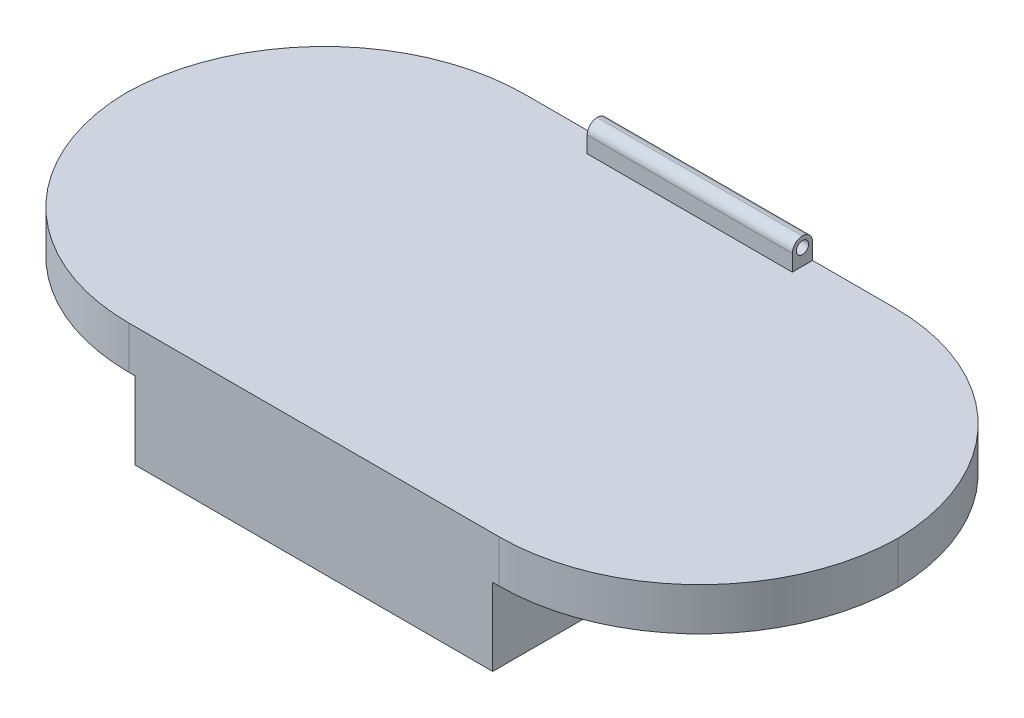
SolidWorks part; units mm, degrees
ref_plane "Front Plane" through (0, 0, 0) normal (0, 0, 1) x (1, 0, 0)
ref_plane "Top Plane" through (0, 0, 0) normal (0, 1, 0) x (1, 0, 0)
ref_plane "Right Plane" through (0, 0, 0) normal (1, 0, 0) x (0, 0, -1)
sketch "Sketch1" plane through (0, 0, 0) normal (0, 1, 0) x (1, 0, 0)
  line L1 (190, 97.5) -> (-190, 97.5)
  line L2 (190, 97.5) -> (190, -97.5)
  line L3 (190, -97.5) -> (-190, -97.5)
  line L4 (-190, 97.5) -> (-190, -97.5)
  line L5 (190, 97.5) -> (-190, -97.5) construction
  line L6 (190, -97.5) -> (-190, 97.5) construction
  point P0 (0, 0)
  dimension "D1" = 380
  dimension "D2" = 195
extrude "Boss-Extrude1" add sketch "Sketch1" along normal blind 59
sketch "Sketch2" plane through (190, 0, 0) normal (1, 0, 0) x (0, 0, -1)
  line L0 (-97.5, 59) -> (-97.5, 0) construction
  line L1 (97.5, 38) -> (-97.5, 38)
  line L2 (97.5, 38) -> (97.5, 0)
  line L3 (97.5, 0) -> (-97.5, 0)
  line L4 (-97.5, 38) -> (-97.5, 0)
  line L5 (97.5, 38) -> (-97.5, 0) construction
  line L6 (97.5, 0) -> (-97.5, 38) construction
  line L7 (-97.5, 59) -> (97.5, 59) construction
  line L8 (-97.5, 0) -> (97.5, 0) construction
  point P0 (0, 19)
  dimension "D1" = 21
  dimension "D2" = 0
extrude "Cut-Extrude1" cut sketch "Sketch2" against normal blind 102
mirror "Mirror1" about plane through (0, 0, 0) normal (1, 0, 0) of "Cut-Extrude1"
fillet "Fillet1" radius 99 4 edges at (-190, 48.5, 97.5) (-190, 48.5, -97.5) (190, 48.5, -97.5) (190, 48.5, 97.5)
sketch "Sketch3" plane through (0, 59, 0) normal (0, 1, 0) x (1, 0, 0)
  line L0 (91, 97.5) -> (-91, 97.5) construction
  line L1 (50.5, 97.5) -> (-50.5, 97.5)
  line L2 (50.5, 97.5) -> (50.5, 87.5)
  line L3 (50.5, 87.5) -> (-50.5, 87.5)
  line L4 (-50.5, 97.5) -> (-50.5, 87.5)
  line L5 (50.5, 97.5) -> (-50.5, 87.5) construction
  line L6 (50.5, 87.5) -> (-50.5, 97.5) construction
  point P0 (0, 92.5)
  dimension "D1" = 0
  dimension "D2" = 10
  dimension "D3" = 101
  dimension "D4" = 0
extrude "Boss-Extrude2" add sketch "Sketch3" along normal blind 13
fillet "Fillet2" radius 5 2 edges at (0, 72, -97.5) (0, 72, -87.5)
sketch "Sketch4" plane through (-50.5, 0, 0) normal (-1, 0, 0) x (0, 0, 1)
  circle A0 centre (-92.5, 67) radius 3
  dimension "D1" = 6
extrude "Cut-Extrude2" cut sketch "Sketch4" against normal blind 112
